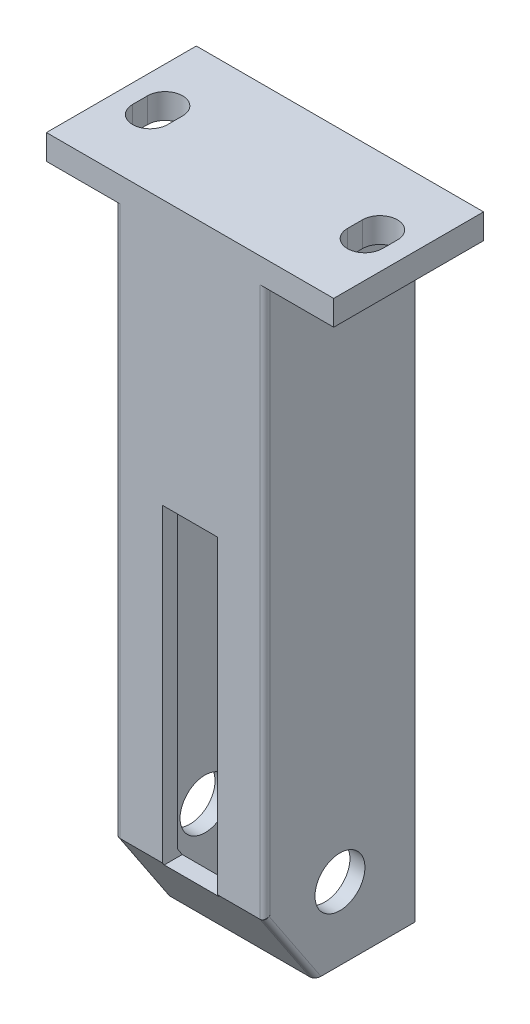
SolidWorks part; units mm, degrees
material "普通碳钢"
ref_plane "Front" through (0, 0, 0) normal (0, 0, 1) x (1, 0, 0)
ref_plane "Top" through (0, 0, 0) normal (0, 1, 0) x (1, 0, 0)
ref_plane "Right" through (0, 0, 0) normal (1, 0, 0) x (0, 0, -1)
sketch "草图1" plane through (0, 0, 0) normal (0, 1, 0) x (1, 0, 0)
  line L0 (-57.5, 30) -> (57.5, 30) construction
  line L1 (-57.5, 0) -> (57.5, 0)
  line L2 (-57.5, 0) -> (-57.5, 60)
  line L3 (-57.5, 60) -> (57.5, 60)
  line L4 (57.5, 0) -> (57.5, 60)
  line L5 (0, 0) -> (0, 60) construction
  line L6 (43, 0) -> (43, 60) construction
  line L7 (-43, 0) -> (-43, 60) construction
  line L8 (36, 33) -> (36, 27)
  line L9 (50, 33) -> (50, 27)
  line L10 (-50, 33) -> (-50, 27)
  line L11 (-36, 33) -> (-36, 27)
  arc A2 (-36, 33) -> (-50, 33) centre (-43, 33) ccw
  arc A4 (50, 33) -> (36, 33) centre (43, 33) ccw
  arc A5 (36, 27) -> (50, 27) centre (43, 27) ccw
  arc A6 (-50, 27) -> (-36, 27) centre (-43, 27) ccw
  dimension "D5" = 14
  dimension "D1" = 115
  dimension "D2" = 60
  dimension "D3" = 43
  dimension "D6" = 3
  dimension "D7" = 3
  dimension "D8" = 3
  dimension "D9" = 3
  dimension "D4" = 43
extrude "凸台-拉伸1" add sketch "草图1" along normal blind 10
sketch "草图2" plane through (0, 0, 0) normal (0, -1, 0) x (1, 0, 0)
  line L5 (-30, -2) -> (-30, -60)
  line L6 (-57.5, 0) -> (57.5, 0) construction
  line L8 (30, -2) -> (30, -60)
  line L10 (-28, 0) -> (28, 0)
  line L12 (-22, -6) -> (22, -6)
  line L13 (24, -8) -> (24, -60)
  line L15 (-24, -8) -> (-24, -60)
  line L16 (24, -6) -> (24, -54) construction
  line L17 (-24, -54) -> (24, -54) construction
  line L18 (-24, -6) -> (-24, -54) construction
  line L19 (-24, -6) -> (24, -6) construction
  line L20 (-28, -60) -> (28, -60) construction
  line L21 (57.5, -60) -> (-57.5, -60) construction
  line L22 (-30, -60) -> (-24, -60)
  line L23 (24, -60) -> (30, -60)
  arc A0 (-30, -2) -> (-28, 0) centre (-28, -2) cw
  arc A2 (30, -2) -> (28, 0) centre (28, -2) ccw
  arc A6 (-24, -8) -> (-22, -6) centre (-22, -8) cw
  arc A7 (22, -6) -> (24, -8) centre (22, -8) cw
  arc A9 (24, -54) -> (24, -54) centre (24, -54) cw construction
  arc A10 (-24, -54) -> (-24, -54) centre (-24, -54) ccw construction
  arc A11 (-24, -6) -> (-24, -6) centre (-24, -6) cw construction
  arc A12 (24, -6) -> (24, -6) centre (24, -6) ccw construction
  arc A13 (30, -60) -> (28, -60) centre (29, -58.2679) cw construction
  arc A14 (-30, -60) -> (-28, -60) centre (-29, -58.2679) ccw construction
  point P10 (-30, 0)
  point P18 (30, 0)
  dimension "D3" = 2
  dimension "D5" = 2
  dimension "D6" = 2
  dimension "D1" = 30
  dimension "D2" = 30
  dimension "D4" = 6
extrude "凸台-拉伸2" add sketch "草图2" along normal blind 250
sketch "草图3" plane through (30, 0, 0) normal (1, 0, 0) x (0, 0, -1)
  line L0 (20, -250) -> (0, -250)
  line L1 (60, -250) -> (2, -250) construction
  line L2 (0, -250) -> (0, -220)
  line L3 (0, -250) -> (0, 0) construction
  line L4 (0, -220) -> (20, -250)
  dimension "D1" = 30
  dimension "D2" = 20
extrude "切除-拉伸1" cut sketch "草图3" against normal up to surface (60 mm away) up to face at (-30, -125, -31)
sketch "草图4" plane through (30, 0, 0) normal (1, 0, 0) x (0, 0, -1)
  line L0 (20, -250) -> (0, -220)
  line L1 (0, -220) -> (4.9923, -216.6718)
  line L2 (4.9923, -216.6718) -> (27.2111, -250)
  line L3 (60, -250) -> (20, -250) construction
  line L4 (27.2111, -250) -> (20, -250)
  dimension "D1" = 6
extrude "凸台-拉伸3" add sketch "草图4" against normal up to surface (60 mm away) up to face at (-30, -144.6, -28.8)
fillet "圆角1" radius 2 7 edges at (24, -235.5917, -17.6056) (23.4142, -219.062, -6.5858) (0, -218.1833, -6) (-23.4142, -219.062, -6.5858) (-24, -235.5917, -17.6056) (-30, -235, -10) (30, -235, -10)
sketch "草图5" plane through (30, 0, 0) normal (1, 0, 0) x (0, 0, -1)
  line L0 (60, -250) -> (22.4037, -250) construction
  line L2 (60, -250) -> (60, 0) construction
  circle A0 centre (30, -221) radius 10
  dimension "D1" = 20
  dimension "D2" = 29
  dimension "D3" = 30
extrude "切除-拉伸2" cut sketch "草图5" against normal up to surface (60 mm away) up to face at (-30, -156.2595, -24.678)
sketch "草图6" plane through (0, 0, 0) normal (0, 0, 1) x (1, 0, 0)
  line L0 (-57.5, 10) -> (57.5, 10) construction
  line L1 (-11, -96) -> (11, -96)
  line L2 (-11, -96) -> (-11, -221)
  line L3 (-11, -221) -> (11, -221)
  line L4 (11, -96) -> (11, -221)
  line L5 (-30, -218.6667) -> (-30, 0) construction
  line L6 (30, -218.6667) -> (30, 0) construction
  line L7 (28, -250) -> (-28, -250) construction
  dimension "D1" = 106
  dimension "D2" = 19
  dimension "D3" = 19
  dimension "D4" = 29
extrude "切除-拉伸3" cut sketch "草图6" against normal up to next
